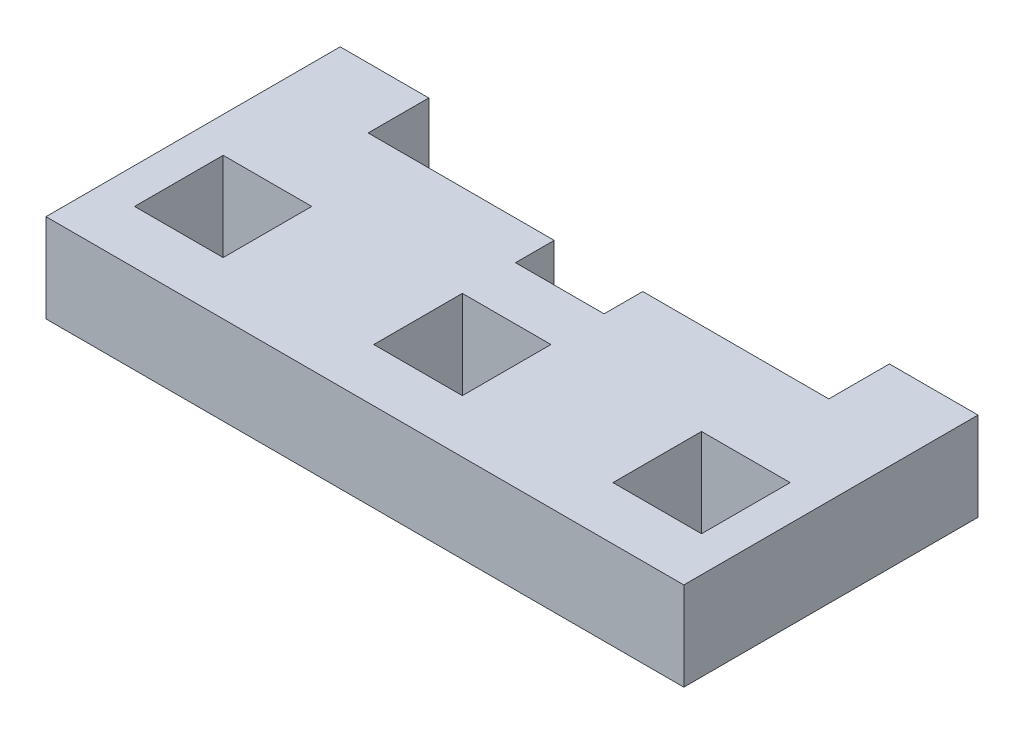
SolidWorks part; units mm, degrees
ref_plane "Front Plane" through (0, 0, 0) normal (0, 0, 1) x (1, 0, 0)
ref_plane "Top Plane" through (0, 0, 0) normal (0, 1, 0) x (1, 0, 0)
ref_plane "Right Plane" through (0, 0, 0) normal (1, 0, 0) x (0, 0, -1)
sketch "Sketch1" plane through (0, 0, 0) normal (0, 1, 0) x (1, 0, 0)
  line L0 (-22.86, 0) -> (22.86, 0) construction
  line L1 (-22.86, -6.985) -> (22.86, -6.985)
  line L2 (-22.86, -6.985) -> (-22.86, 9.7575)
  line L3 (-16.51, 9.7575) -> (-3.175, 9.7575)
  line L4 (22.86, -6.985) -> (22.86, 9.7575)
  line L5 (0, 6.985) -> (0, -6.985) construction
  line L6 (-3.175, 9.7575) -> (-3.175, 6.985)
  line L7 (-3.175, 6.985) -> (3.175, 6.985)
  line L8 (3.175, 6.985) -> (3.175, 9.7575)
  line L9 (3.175, 9.7575) -> (16.51, 9.7575)
  line L10 (-20.32, 3.175) -> (-13.97, -3.175) construction
  line L11 (-3.175, 3.175) -> (3.175, 3.175)
  line L12 (-3.175, 3.175) -> (-3.175, -3.175)
  line L13 (-3.175, -3.175) -> (3.175, -3.175)
  line L15 (22.86, 9.7575) -> (22.86, 14.1025)
  line L16 (3.175, 3.175) -> (3.175, -3.175)
  line L17 (-3.175, 3.175) -> (3.175, -3.175) construction
  line L18 (-3.175, -3.175) -> (3.175, 3.175) construction
  line L19 (-13.97, 3.175) -> (-20.32, -3.175) construction
  line L20 (13.97, 3.175) -> (20.32, -3.175) construction
  line L21 (13.97, -3.175) -> (20.32, 3.175) construction
  line L22 (20.32, -3.175) -> (13.97, -3.175)
  line L23 (20.32, -3.175) -> (20.32, 3.175)
  line L24 (20.32, 3.175) -> (13.97, 3.175)
  line L25 (13.97, -3.175) -> (13.97, 3.175)
  line L26 (22.86, 14.1025) -> (16.51, 14.1025)
  line L27 (16.51, 14.1025) -> (16.51, 9.7575)
  line L28 (-16.51, 14.1025) -> (-16.51, 9.7575)
  line L29 (-22.86, 14.1025) -> (-16.51, 14.1025)
  line L30 (-13.97, -3.175) -> (-13.97, 3.175)
  line L31 (-20.32, 3.175) -> (-13.97, 3.175)
  line L32 (-20.32, -3.175) -> (-20.32, 3.175)
  line L33 (-20.32, -3.175) -> (-13.97, -3.175)
  line L34 (-22.86, 9.7575) -> (-22.86, 14.1025)
  point P8 (0, 0)
  point P12 (0, 6.985)
  point P16 (0, 0)
  point P22 (-17.145, 0)
  point P23 (17.145, 0)
  dimension "D1" = 45.72
  dimension "D2" = 3.81
  dimension "D3" = 6.35
  dimension "D4" = 3.81
  dimension "D5" = 13.97
  dimension "D6" = 6.35
  dimension "D7" = 2.54
  dimension "D8" = 10.795
  dimension "D9" = 2.7725
  dimension "D10" = 4.345
  dimension "D11" = 6.35
  dimension "D12" = 21.0875
extrude "Boss-Extrude1" add sketch "Sketch1" along normal blind 6.35
equation "\"Ball Diameter\"= 1.75in"
equation "\"Sheet Thickness\"= 0.25in"
equation "\"Screw Diameter\"= .17in"
equation "\"Robot Diameter\"= 14in"
equation "\"Castor Screw Diameter\"= 0.22in"
equation "\"Wheel Diameter\" = 4in"
equation "\"Nut Diameter\" = 8.4mm"
equation "\"Nut Height\" = 2.9mm"
equation "\"Screw Height\" = 0.55in"
equation "\"Pulley Diameter\" = 1in"
equation "\"Reactor Height\" = 14in"
equation "\"Elevator Height\" = 11.5in"
equation "\"Elevator Width\" = \"Ball Diameter\" + 0.25in"
equation "\"Elevator Bearing Diameter\" = sqr(2*(\"Sheet Thickness\"^2)) + 0.2in"
equation "\"Elevator Axle Endcap Diameter\" = \"Pulley Diameter\" + 0.25in"
equation "\"Elevator Axle Length\" = \"Elevator Width\" + 8*\"Sheet Thickness\""
equation "\"Elevator Clearance from Axis\" = 3.28in"
equation "\"D1@Sketch1\"=\"Elevator Width\"-0.2in"
equation "\"D3@Sketch1\" = \"Sheet Thickness\""
equation "\"D6@Sketch1\"=\"Sheet Thickness\""
equation "\"D9@Sketch1\"=(0.3in - ((\"Elevator Axle Endcap Diameter\"-\"Pulley Diameter\")/2 - 1.1mm))/2"
equation "\"D10@Sketch1\"=(\"Elevator Axle Endcap Diameter\"-\"Pulley Diameter\")/2 - 1.1mm + 2.27mm"
equation "\"D1@Boss-Extrude1\"=\"Sheet Thickness\""
equation "\"Ball Radius\" = \"Ball Diameter\"/2"
equation "\"Claw Horizontal Seperation\" = (\"Elevator Width\"/2) - (1.5 * \"Sheet Thickness\") - 0.15in"
